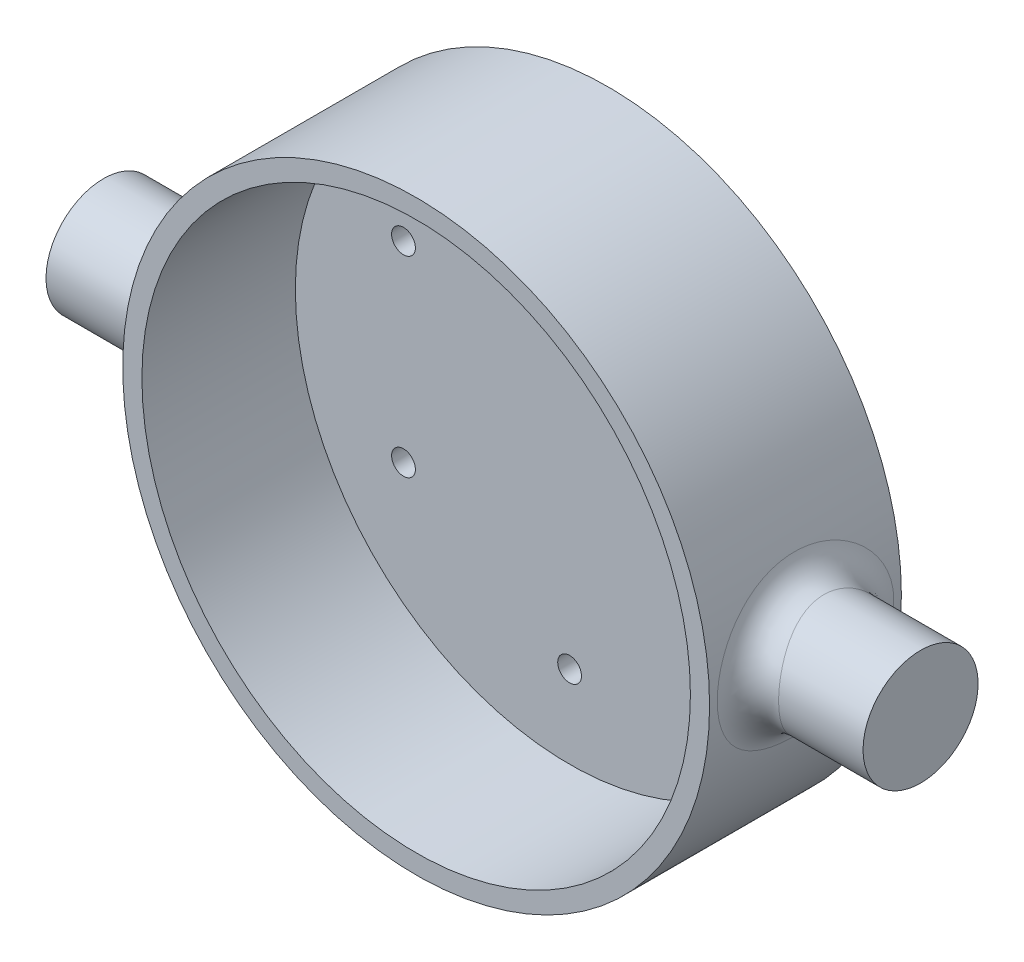
SolidWorks part; units mm, degrees
ref_plane "Alzado" through (0, 0, 0) normal (0, 0, 1) x (1, 0, 0)
ref_plane "Planta" through (0, 0, 0) normal (0, 1, 0) x (1, 0, 0)
ref_plane "Vista lateral" through (0, 0, 0) normal (1, 0, 0) x (0, 0, -1)
sketch "Croquis1" plane through (0, 0, 0) normal (0, 0, 1) x (1, 0, 0)
  circle A0 centre (0, 0) radius 38.25
  dimension "D1" = 76.5
extrude "Saliente-Extruir1" add sketch "Croquis1" along normal mid plane 25
sketch "Croquis2" plane through (0, 0, 12.5) normal (0, 0, 1) x (1, 0, 0)
  circle A0 centre (0, 0) radius 35.75
  dimension "D1" = 71.5
extrude "Cortar-Extruir1" cut sketch "Croquis2" against normal blind 20
sketch "Croquis4" plane through (0, 0, 0) normal (0, 0, 1) x (1, 0, 0)
  line L0 (38.25, 0) -> (53.25, 0) construction
  line L1 (53.25, 0) -> (53.25, 7.5)
  line L2 (53.25, 7.5) -> (37.5075, 7.5)
  line L3 (38.25, 0) -> (53.25, 0)
  circle A0 centre (0, 0) radius 38.25 construction
  arc A1 (38.25, 0) -> (37.5075, 7.5) centre (0, 0) ccw
  point P2 (53.25, 3.75)
  dimension "D1" = 15
  dimension "D2" = 15
revolve "Revolución1" add sketch "Croquis4" angle 360 about L0
fillet "Redondeo1" radius 4 1 edges at (38.218, 1.5647, -7.335)
mirror "Simetría1" about plane through (0, 0, 0) normal (1, 0, 0) of "Revolución1", "Redondeo1"
sketch "Croquis5" plane through (0, 0, -12.5) normal (0, 0, -1) x (-1, 0, 0)
  circle A0 centre (0, 0) radius 25 construction
  circle A2 centre (0, 25) radius 1.55
  circle A3 centre (21.6506, 12.5) radius 1.55
  circle A4 centre (21.6506, -12.5) radius 1.55
  circle A5 centre (0, -25) radius 1.55
  circle A6 centre (-21.6506, -12.5) radius 1.55
  circle A7 centre (-21.6506, 12.5) radius 1.55
  point P18 (0, 0)
  dimension "D1" = 50
  dimension "D2" = 3.1
  dimension "D3" = 6
extrude "Cortar-Extruir2" cut sketch "Croquis5" against normal up to surface (5 mm away) up to face at (35.75, 0, -7.5)
